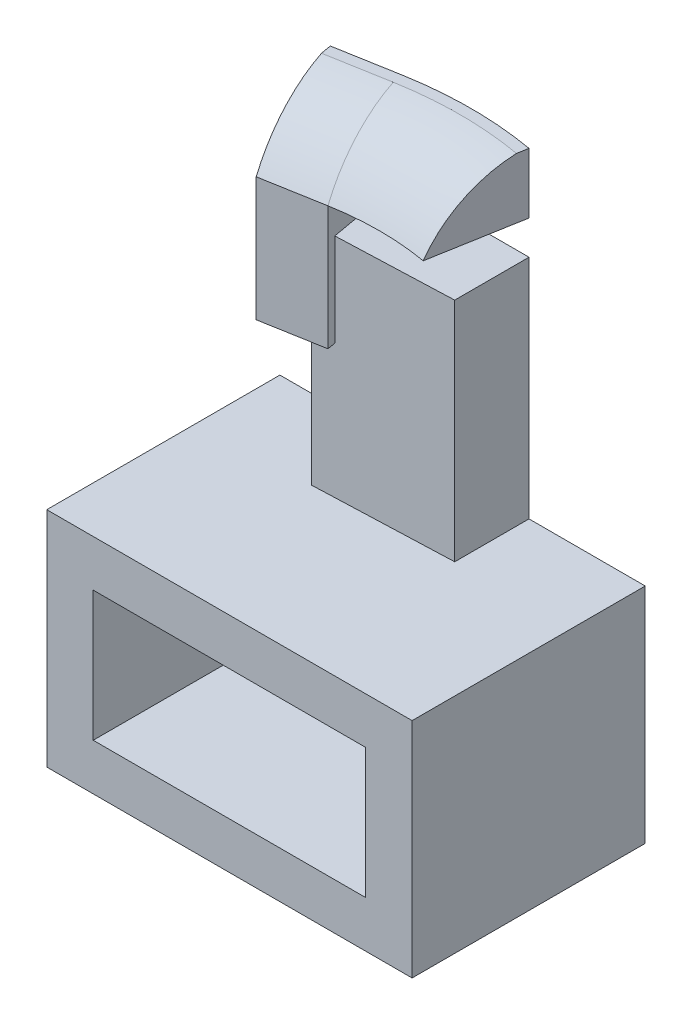
SolidWorks part; units mm, degrees
ref_plane "Front Plane" through (0, 0, 0) normal (0, 0, 1) x (1, 0, 0)
ref_plane "Top Plane" through (0, 0, 0) normal (0, 1, 0) x (1, 0, 0)
ref_plane "Right Plane" through (0, 0, 0) normal (1, 0, 0) x (0, 0, -1)
sketch "Sketch1" plane through (0, 0, 0) normal (0, 0, 1) x (1, 0, 0)
  line L1 (22, -10.5) -> (-22, -10.5)
  line L2 (22, -10.5) -> (22, 10.5)
  line L3 (22, 10.5) -> (-22, 10.5)
  line L4 (-22, -10.5) -> (-22, 10.5)
  line L5 (22, -10.5) -> (-22, 10.5) construction
  line L6 (22, 10.5) -> (-22, -10.5) construction
  line L7 (29.5, -18) -> (-29.5, -18)
  line L8 (29.5, -18) -> (29.5, 18)
  line L9 (29.5, 18) -> (-29.5, 18)
  line L10 (-29.5, -18) -> (-29.5, 18)
  point P0 (0, 0)
  point P6 (0, 0)
  dimension "D1" = 44
  dimension "D2" = 21
  dimension "D3" = 7.5
  dimension "D4" = 7.5
  dimension "D5" = 7.5
  dimension "D6" = 7.5
extrude "Boss-Extrude1" add sketch "Sketch1" along normal blind 10
extrude "Boss-Extrude2" add sketch "Sketch1<2>" against normal blind 5 contours L10 L7 L8 L9 L1 L4 L3 L2 | L4 L1 L2 L3 region at (0, 0, 0) region at (0, -17.3088, 0)
sketch "Sketch1<2>" plane through (0, 0, 0) normal (0, 0, 1) x (1, 0, 0) same geometry as "Sketch1"
sketch "Sketch4" plane through (0, 18, 0) normal (0, 1, 0) x (1, 0, 0)
  line L0 (0, -21.3149) -> (0, 19.6679) construction
  line L1 (29.5, -10) -> (-29.5, -10) construction
  line L2 (-11.5916, 5) -> (-11.5916, -7.8447)
  line L3 (-11.5916, 5) -> (10.7314, 5)
  line L4 (-11.5916, -7.8447) -> (10.7314, -7)
  line L5 (10.7314, 5) -> (10.7314, -7)
  line L6 (-11.5916, 5) -> (10.7314, -7) construction
  line L7 (-11.5916, -7.8447) -> (10.7314, 5) construction
  line L8 (29.5, 5) -> (-29.5, 5) construction
  point P5 (0, -10)
  point P6 (-0.0506, -1.204)
  dimension "D1" = 12
extrude "Boss-Extrude3" add sketch "Sketch4" along normal blind 36.6
sketch "Sketch6" plane through (0, 0, 0) normal (1, 0, 0) x (0, 0, -1)
  line L0 (-1, 152.0077) -> (-1, -32.8077) construction
  line L1 (-7, 54.6) -> (5, 54.6) construction
  line L2 (6.375, 59.6) -> (-8.375, 59.6)
  line L3 (6.375, 59.6) -> (6.375, 69.35)
  line L4 (6.375, 69.35) -> (4.625, 69.35)
  arc A0 (4.625, 69.35) -> (-8.375, 59.6) centre (8.9258, 50.074) ccw
  point P2 (-1, 59.6)
  point P5 (-1, 54.6)
  dimension "D1" = 9.75
  dimension "D4" = 19.75
  dimension "D2" = 14.75
  dimension "D3" = 1.75
  dimension "D5" = 5
sketch "Sketch7" plane through (0, 0, 0) normal (1, 0, 0) x (0, 0, -1)
  line L0 (-52.68, 146.6711) -> (-52.68, -25.9306) construction
  line L1 (-1, 152.0077) -> (-1, -32.8077) construction
  dimension "D1" = 51.68
revolve "Revolve1" add sketch "Sketch6" angle 20 mid plane about L0
sketch "Sketch8" plane through (-9.0088, 0, 1.5885) normal (-0.9848, 0, 0.1736) x (0.1736, 0, 0.9848)
  line L0 (-7.1753, 69.35) -> (-7.1753, 59.6)
  line L1 (-7.1753, 59.6) -> (-7.1753, 39.6)
  line L2 (-7.1753, 39.6) -> (7.5747, 39.6)
  line L3 (7.5747, 39.6) -> (7.5747, 59.6)
  line L4 (-7.1753, 69.35) -> (-5.4253, 69.35) construction
  line L5 (-5.4253, 69.35) -> (-7.1753, 69.35)
  line L6 (5.7126, 54.6) -> (8.7571, 54.6) construction
  arc A0 (7.5747, 59.6) -> (-5.4253, 69.35) centre (-9.8905, 49.8548) ccw
  arc A1 (7.5747, 59.6) -> (-5.4253, 69.35) centre (-9.7261, 50.074) ccw construction
  dimension "D1" = 15
extrude "Boss-Extrude4" add sketch "Sketch8" along normal blind 10
extrude "Boss-Extrude6" add sketch "Sketch1<5>" along normal blind 7.65 contours L4 L1 L2 L3 region at (0, 0, 0)
sketch "Sketch1<5>" plane through (0, 0, 0) normal (0, 0, 1) x (1, 0, 0) same geometry as "Sketch1"
extrude "Boss-Extrude7" add sketch "Sketch1<6>" along normal blind 25 from surface starting at face at (0, 0, 7.65)
sketch "Sketch1<6>" plane through (0, 0, 0) normal (0, 0, 1) x (1, 0, 0) same geometry as "Sketch1"
